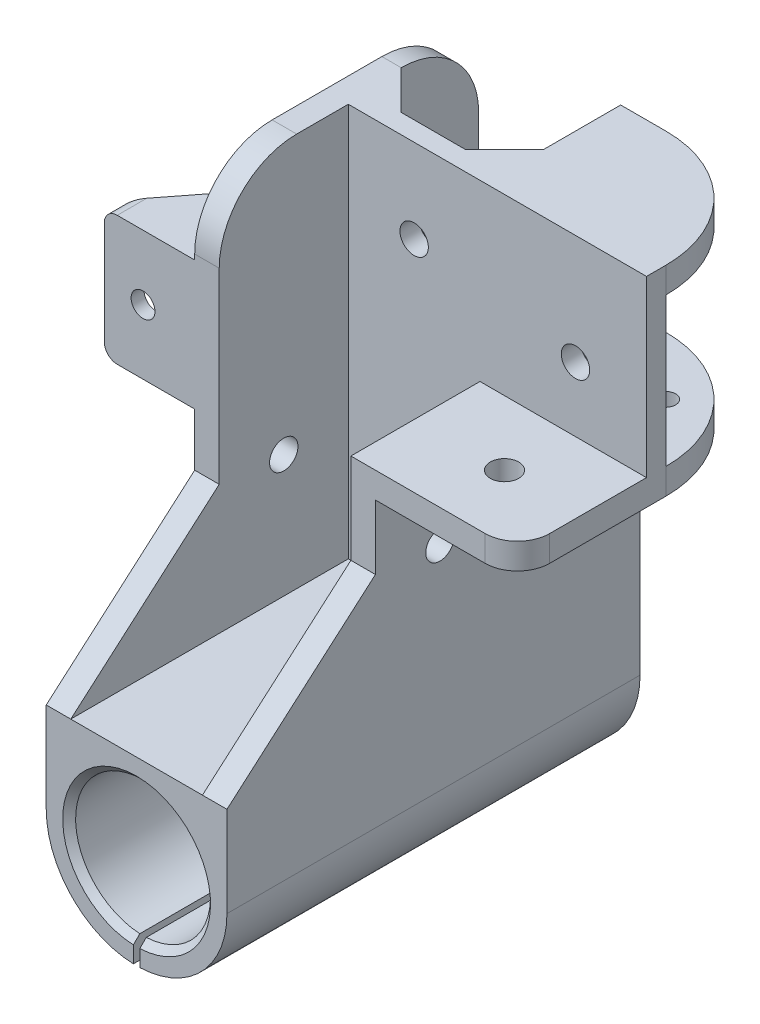
SolidWorks part; units mm, degrees
material "ABS"
ref_plane "Front Plane" through (0, 0, 0) normal (0, 0, 1) x (1, 0, 0)
ref_plane "Top Plane" through (0, 0, 0) normal (0, 1, 0) x (1, 0, 0)
ref_plane "Right Plane" through (0, 0, 0) normal (1, 0, 0) x (0, 0, -1)
sketch "Sketch1" plane through (0, 0, 0) normal (0, 0, 1) x (1, 0, 0)
  line L0 (-14, 0) -> (-14, 75)
  line L3 (-14, 75) -> (36, 75)
  line L4 (14, 44) -> (14, 0)
  line L5 (14, 44) -> (36, 44)
  line L6 (36, 44) -> (36, 75)
  arc A0 (-14, 0) -> (14, 0) centre (0, 0) ccw
  dimension "D3" = 28
  dimension "D1" = 31
  dimension "D4" = 75
  dimension "D5" = 22
extrude "Boss-Extrude1" add sketch "Sketch1" along normal blind 64
sketch "Sketch2" plane through (0, 75, 0) normal (0, 1, 0) x (1, 0, 0)
  line L0 (-11, 0) -> (-11, -12)
  line L1 (36, 0) -> (-14, 0) construction
  line L2 (-11, -12) -> (-5, -18)
  line L3 (-5, -18) -> (5, -18)
  line L4 (5, -18) -> (11, -12)
  line L5 (11, -12) -> (11, 0)
  line L6 (11, 0) -> (-11, 0)
  line L7 (14, -64) -> (14, 0) construction
  dimension "D1" = 10
  dimension "D2" = 22
  dimension "D3" = 3
  dimension "D4" = 12
  dimension "D5" = 18
extrude "Cut-Extrude1" cut sketch "Sketch2" against normal blind 61
sketch "Sketch3" plane through (14, 0, 0) normal (1, 0, 0) x (0, 0, -1)
  line L0 (-64, 14) -> (-41, 34)
  line L1 (-64, 0) -> (-64, 44) construction
  line L2 (-41, 34) -> (-41, 75)
  line L3 (-64, 75) -> (0, 75) construction
  line L4 (-41, 75) -> (-64, 75)
  line L5 (-64, 75) -> (-64, 14)
  dimension "D1" = 23
  dimension "D2" = 41
  dimension "D3" = 61
extrude "Cut-Extrude2" cut sketch "Sketch3" against normal through all both and the other way through all
sketch "Sketch4" plane through (0, 0, 64) normal (0, 0, 1) x (1, 0, 0)
  line L0 (-10.2, 14) -> (-10.2, 75)
  line L1 (-14, 14) -> (14, 14) construction
  line L2 (36, 44) -> (14, 44) construction
  line L4 (-14, 75) -> (36, 75) construction
  line L5 (-10.2, 75) -> (36, 75)
  line L7 (10.2, 48) -> (10.2, 14)
  line L8 (10.2, 14) -> (-10.2, 14)
  line L9 (-14, 14) -> (-14, 34) construction
  line L10 (14, 14) -> (14, 34) construction
  line L12 (10.2, 48) -> (36, 48)
  line L13 (36, 44) -> (36, 75) construction
  line L14 (36, 48) -> (36, 75)
  dimension "D1" = 3.8
  dimension "D2" = 3.8
  dimension "D3" = 4
extrude "Cut-Extrude3" cut sketch "Sketch4" against normal blind 43
sketch "Sketch5" plane through (0, 0, 64) normal (0, 0, 1) x (1, 0, 0)
  line L0 (0, -10.45) -> (0, -14) construction
  line L1 (-0.5, -10.438) -> (-0.5, -13.9911)
  line L2 (0.5, -10.438) -> (0.5, -13.9911)
  line L3 (-0.5, -10.45) -> (-0.5, -17.5466) construction
  line L4 (0, -10.45) -> (0, -17.5466) construction
  line L5 (0.5, -10.45) -> (0.5, -17.5466) construction
  arc A0 (0.5, -10.438) -> (-0.5, -10.438) centre (0, 0) ccw
  arc A1 (-14, 0) -> (14, 0) centre (0, 0) ccw construction
  arc A2 (-0.5, -13.9911) -> (0.5, -13.9911) centre (0, 0) ccw
  dimension "D1" = 20.9
  dimension "D2" = 0.5
  dimension "D3" = 0.5
extrude "Cut-Extrude4" cut sketch "Sketch5" against normal through all
chamfer "Chamfer1" distance 1 angle 45 2 edges at (0, 10.45, 0) (0, 10.45, 64)
sketch "Sketch6" plane through (0, 0, 21) normal (0, 0, 1) x (1, 0, 0)
  line L0 (0, 14) -> (0, 27) construction
  line L1 (-10.2, 14) -> (10.2, 14) construction
  line L4 (10.2, 48) -> (36, 48) construction
  line L5 (36, 48) -> (36, 75) construction
  circle A1 centre (0, 62) radius 2.2
  circle A2 centre (0, 27) radius 2.2
  circle A3 centre (25, 58) radius 2.2
  dimension "D1" = 4.4
  dimension "D2" = 35
  dimension "D7" = 11
  dimension "D3" = 13
  dimension "D6" = 10
extrude "Cut-Extrude5" cut sketch "Sketch6" against normal through all
sketch "Sketch7" plane through (-14, 0, 0) normal (1, 0, 0) x (0, 0, -1)
  line L0 (-41, 62.2) -> (-21, 62.2)
  line L1 (-41, 34) -> (-41, 44) construction
  line L2 (-21, 62.2) -> (-21, 60.2)
  line L3 (-21, 60.2) -> (-39, 60.2)
  line L4 (-39, 60.2) -> (-39, 44.2)
  line L5 (-39, 44.2) -> (-21, 44.2)
  line L6 (-21, 44.2) -> (-21, 42.2)
  line L7 (-21, 42.2) -> (-41, 42.2)
  line L8 (-41, 42.2) -> (-41, 62.2)
  line L9 (-41, 75) -> (0, 75) construction
  dimension "D1" = 20
  dimension "D2" = 12.8
  dimension "D3" = 2
  dimension "D4" = 2
extrude "Boss-Extrude2" add sketch "Sketch7" against normal blind 14
sketch "Sketch8" plane through (0, 62.2, 0) normal (0, 1, 0) x (1, 0, 0)
  line L0 (-14, -21) -> (-28, -39)
  line L1 (-28, -21) -> (-28, -41) construction
  line L2 (-28, -39) -> (-28, -21)
  line L3 (-28, -21) -> (-14, -21)
  line L5 (-28, -41) -> (-14, -41) construction
  dimension "D1" = 2
extrude "Cut-Extrude6" cut sketch "Sketch8" against normal through all
sketch "Sketch9" plane through (0, 0, 41) normal (0, 0, 1) x (1, 0, 0)
  line L0 (-22, 52.2) -> (-28, 52.2) construction
  line L1 (-28, 62.2) -> (-28, 42.2) construction
  line L2 (-28, 62.2) -> (-28, 42.2) construction
  circle A0 centre (-22, 52.2) radius 1.85
  dimension "D1" = 3.7
  dimension "D2" = 6
extrude "Cut-Extrude7" cut sketch "Sketch9" against normal through all
fillet "Fillet1" radius 2 2 edges at (-28, 42.2, 40) (-28, 62.2, 40)
fillet "Fillet2" radius 12 3 edges at (-12.5, 75, 0) (-11, 75, 6) (-12.1, 75, 41)
sketch "Sketch10" plane through (14, 0, 0) normal (1, 0, 0) x (0, 0, -1)
  line L0 (0, 0) -> (0, 44) construction
  line L2 (-21, 75) -> (-29, 75) construction
  circle A0 centre (-31, 33) radius 2.2
  dimension "D1" = 4.4
  dimension "D2" = 31
  dimension "D3" = 42
extrude "Cut-Extrude8" cut sketch "Sketch10" against normal through all
fillet "Fillet3" radius 5 1 edges at (36, 46, 41)
fillet "Fillet4" radius 18 1 edges at (36, 59.5, 0)
sketch "Sketch11" plane through (0, 48, 0) normal (0, 1, 0) x (1, 0, 0)
  line L2 (31, -41) -> (10.2, -41) construction
  line L3 (36, -21) -> (36, -36) construction
  circle A0 centre (24, -31) radius 2.2
  dimension "D1" = 4.4
  dimension "D3" = 10
  dimension "D2" = 12
extrude "Cut-Extrude9" cut sketch "Sketch11" against normal through all
sketch "Sketch12" plane through (36, 0, 0) normal (-1, 0, 0) x (0, 0, 1)
  line L1 (18, 71) -> (0, 71)
  line L2 (18, 71) -> (18, 48)
  line L3 (18, 48) -> (0, 48)
  line L4 (0, 71) -> (0, 48)
  line L8 (29, 75) -> (12, 75) construction
  line L9 (0, 63) -> (0, 0) construction
  dimension "D1" = 4
  dimension "D2" = 23
  dimension "D3" = 18
extrude "Cut-Extrude10" cut sketch "Sketch12" along normal blind 22
sketch "Sketch13" plane through (0, 44, 0) normal (0, -1, 0) x (1, 0, 0)
  circle A0 centre (19, 9) radius 1.5
  circle A2 centre (27, 9) radius 1.5
extrude "Cut-Extrude11" cut sketch "Sketch13" against normal up to next
